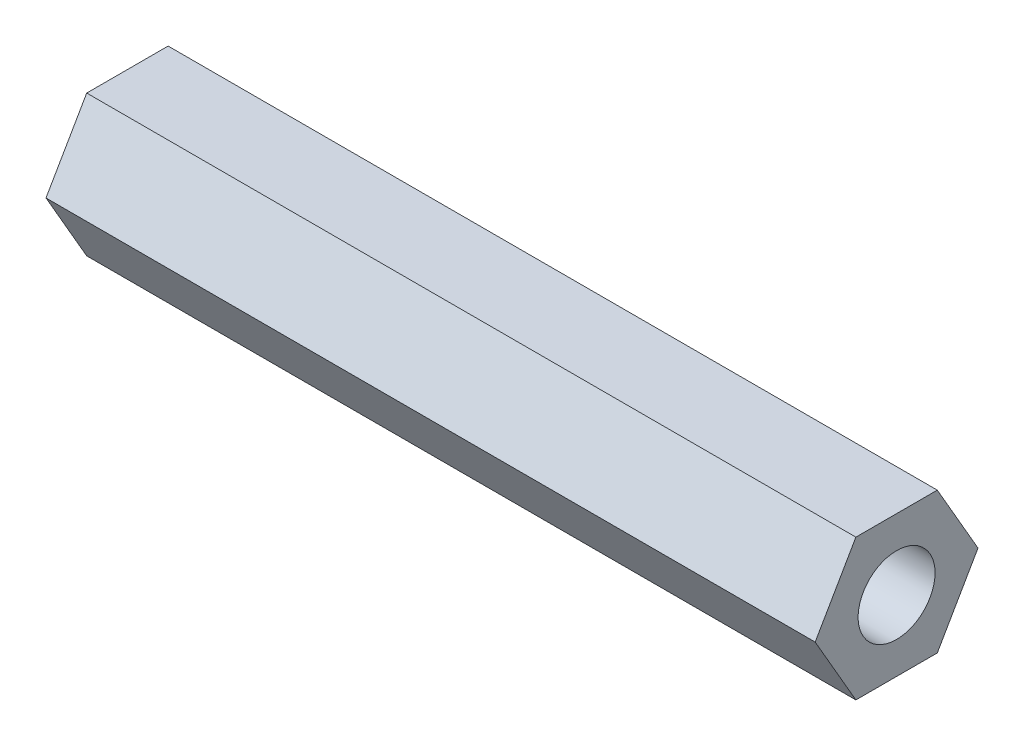
SolidWorks part; units mm, degrees
ref_plane "Front Plane" through (0, 0, 0) normal (0, 0, 1) x (1, 0, 0)
ref_plane "Top Plane" through (0, 0, 0) normal (0, 1, 0) x (1, 0, 0)
ref_plane "Right Plane" through (0, 0, 0) normal (1, 0, 0) x (0, 0, -1)
sketch "Hex Sketch" plane through (0, 0, 0) normal (1, 0, 0) x (0, 0, -1)
  line L0 (3.1754, 0) -> (1.5877, 2.75)
  line L1 (1.5877, 2.75) -> (-1.5877, 2.75)
  line L2 (-1.5877, 2.75) -> (-3.1754, 0)
  line L3 (-3.1754, 0) -> (-1.5877, -2.75)
  line L4 (-1.5877, -2.75) -> (1.5877, -2.75)
  line L5 (1.5877, -2.75) -> (3.1754, 0)
extrude "Hex" add sketch "Hex Sketch" along normal blind 30
ref_axis "Engine Axis" through (31.5, 0, 0) along (-1, 0, 0)
sketch "Bore Sketch" plane through (0, 0, 0) normal (0, 0, 1) x (1, 0, 0)
  line L0 (-400, 0) -> (400, 0) construction
  line L1 (-1, 0) -> (31, 0)
  line L2 (31, 0) -> (31, 1.5)
  line L3 (31, 1.5) -> (-1, 1.5)
  line L4 (-1, 1.5) -> (-1, 0)
revolve "Bore" cut sketch "Bore Sketch" angle 360 about L0
